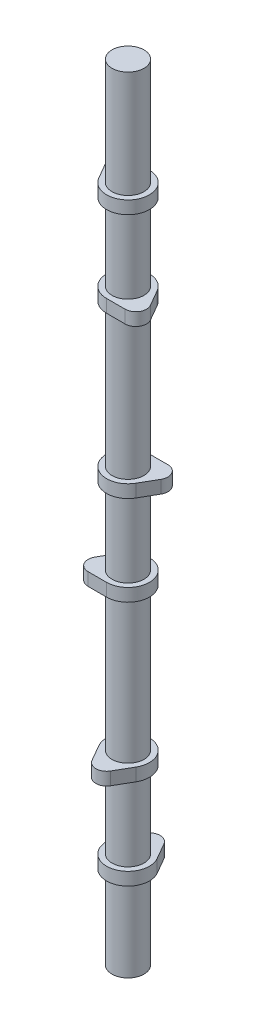
SolidWorks part; units mm, degrees
ref_plane "Front Plane" through (0, 0, 0) normal (0, 0, 1) x (1, 0, 0)
ref_plane "Top Plane" through (0, 0, 0) normal (0, 1, 0) x (1, 0, 0)
ref_plane "Right Plane" through (0, 0, 0) normal (1, 0, 0) x (0, 0, -1)
sketch "Sketch1" plane through (0, 0, 0) normal (0, 1, 0) x (1, 0, 0)
  line L0 (-5.4993, 15.875) -> (-10.9985, 6.35)
  line L1 (5.4993, 15.875) -> (10.9985, 6.35)
  arc A0 (-10.9985, 6.35) -> (10.9985, 6.35) centre (0, 0) ccw
  arc A1 (5.4993, 15.875) -> (-5.4993, 15.875) centre (0, 12.7) ccw
  dimension "D1" = 12.7
  dimension "D2" = 12.7
  dimension "D3" = 25.4
extrude "Boss-Extrude1" add sketch "Sketch1" along normal blind 7.62
ref_axis "Axis1" through (0, 29.0433, 0) along (0, -1, 0)
pattern_linear "LPattern1" count 2 spacing 53.34 along (0, 1, 0) of bodies 101
move or copy body "Body-Move/Copy2" bodies to move or copy 102 copy no rotation origin (0, 0, 0) rotation axis (0, 1, 0) rotation angle 180
pattern_linear "LPattern2" count 3 spacing 146.05 along (0, 1, 0) of bodies 101 104
move or copy body "Body-Move/Copy3" bodies to move or copy 105 107 copy no rotation origin (0, 0, 0) rotation axis (0, 1, 0) rotation angle 120
move or copy body "Body-Move/Copy4" bodies to move or copy 106 108 copy no rotation origin (0, 0, 0) rotation axis (0, -1, 0) rotation angle 120
sketch "Sketch3" plane through (0, 0, 0) normal (0, 1, 0) x (1, 0, 0)
  circle A0 centre (0, 0) radius 9.5
  dimension "D1" = 19
extrude "Boss-Extrude2" add sketch "Sketch3" along normal blind 466.09 from offset 49.53 offset against normal yes
